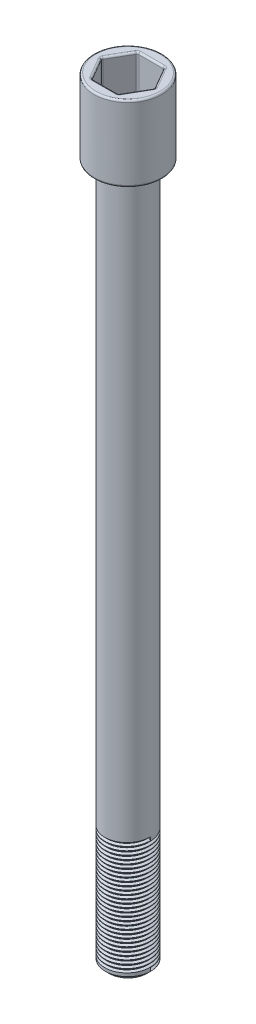
SolidWorks part; units mm, degrees
material "AISI 4140 Steel, quenched & tempered"
ref_plane "Front Plane" through (0, 0, 0) normal (1, 0, 0) x (0, 1, 0)
ref_plane "Top Plane" through (0, 0, 0) normal (0, 0, 1) x (0, 1, 0)
ref_plane "Right Plane" through (0, 0, 0) normal (0, 1, 0) x (-1, 0, 0)
sketch "Sketch1" plane through (0, 0, 0) normal (1, 0, 0) x (0, 1, 0)
  line L0 (-122.9929, 0) -> (42.9358, 0) construction
  line L1 (0, 23.268) -> (0, -20.4189) construction
  line L2 (10, 0) -> (10, 4.5)
  line L3 (10, 4.5) -> (0, 4.5)
  line L4 (0, 4.5) -> (0, 3)
  line L5 (0, 3) -> (-92, 3)
  line L6 (-92, 3) -> (-92, 0)
  line L7 (-92, 0) -> (10, 0)
  dimension "D1" = 10
  dimension "D2" = 9
  dimension "D3" = 6
  dimension "D4" = 92
revolve "Revolve1" add sketch "Sketch1" angle 360 about L0
sketch "Sketch2" plane through (0, 10, 0) normal (0, 1, 0) x (-1, 0, 0)
  line L1 (1.75, -3.0311) -> (3.5, 0)
  line L2 (3.5, 0) -> (1.75, 3.0311)
  line L3 (1.75, 3.0311) -> (-1.75, 3.0311)
  line L4 (-1.75, 3.0311) -> (-3.5, 0)
  line L5 (-3.5, 0) -> (-1.75, -3.0311)
  line L6 (-1.75, -3.0311) -> (1.75, -3.0311)
  circle A0 centre (0, 0) radius 3.0311 construction
  dimension "D1" = 3.5
extrude "Cut-Extrude1" cut sketch "Sketch2" against normal blind 8
ref_axis "Axis1" through (0, 16, 0) along (0, -1, 0)
thread "Thread2" pitch 0.5 method cut profile "Thread Profile2" start angle 0, offset 0.5, length 15, pitch 0.5, diameter 6
ref_plane "Plane2" through (3, -91.5, 0) normal (0, 0, 1) x (1, 0, 0)
sketch "Thread Profile2" plane through (3, -91.5, 0) normal (0, 0, 1) x (1, 0, 0)
  line L0 (0, 0) -> (0, 0.5) construction
  line L11 (0, 0) -> (0, 0.4375)
  line L12 (0, 0.4375) -> (-0.2706, 0.2812)
  line L13 (-0.2706, 0.2812) -> (-0.2706, 0.1562)
  line L15 (-0.2706, 0.1562) -> (0, 0)
  line L17 (-0.2706, 0.2187) -> (0, 0.2187) construction
  point P2 (0, 0)
  dimension "Pitch" = 0.5
  dimension "Profile_Angle" = 60
  dimension "Profile_Land" = 0.125
  dimension "Profile_Height" = 0.2706
chamfer "Chamfer1" distance 0.5 angle 45 1 edges at (0, -92, -3)
fillet "Fillet1" radius 0.25 20 edges at (0, 0, -4.5) (0, 10, -4.5) (0, 10, -3.0311) (-2.625, 10, -1.5155) (-2.625, 10, 1.5155) (0, 10, 3.0311) (2.625, 10, 1.5155) (2.625, 10, -1.5155) (0, 2, -3.0311) (-2.625, 2, -1.5155) (-2.625, 2, 1.5155) (0, 2, 3.0311) (2.625, 2, 1.5155) (2.625, 2, -1.5155) (-1.75, 6, -3.0311) (-1.75, 6, 3.0311) (1.75, 6, 3.0311) (3.5, 6, 0) (1.75, 6, -3.0311) (-3.5, 6, 0)
